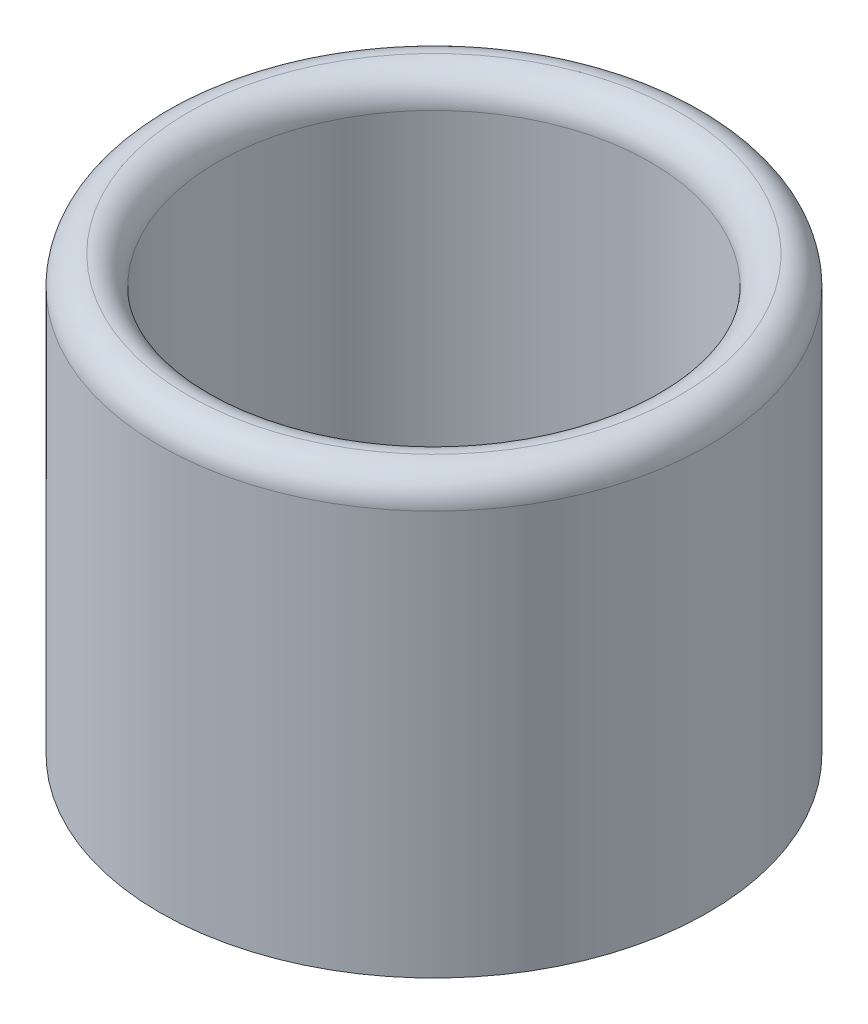
SolidWorks part; units mm, degrees
ref_plane "前视基准面" through (0, 0, 0) normal (0, 0, 1) x (1, 0, 0)
ref_plane "上视基准面" through (0, 0, 0) normal (0, 1, 0) x (1, 0, 0)
ref_plane "右视基准面" through (0, 0, 0) normal (1, 0, 0) x (0, 0, -1)
sketch "草图1" plane through (0, 0, 0) normal (0, 1, 0) x (1, 0, 0)
  circle A77 centre (0, 48.853) radius 1.5
  circle A118 centre (0, 48.853) radius 3
  circle A126 centre (0, 48.853) radius 3.8
extrude "凸台-拉伸1" add sketch "草图1" along normal blind 6 contours A126 A118 region at (-3.6925, 0, -48.853)
extrude "凸台-拉伸2" add sketch "草图1<13>" along normal blind 0.8 contours A118 A77 region at (-2.9151, 0, -48.853)
sketch "草图1<13>" plane through (0, 0, 0) normal (0, 1, 0) x (1, 0, 0) same geometry as "草图1"
fillet "圆角1" radius 0.4 2 edges at (0, 6, -45.053) (0, 6, -45.853)
